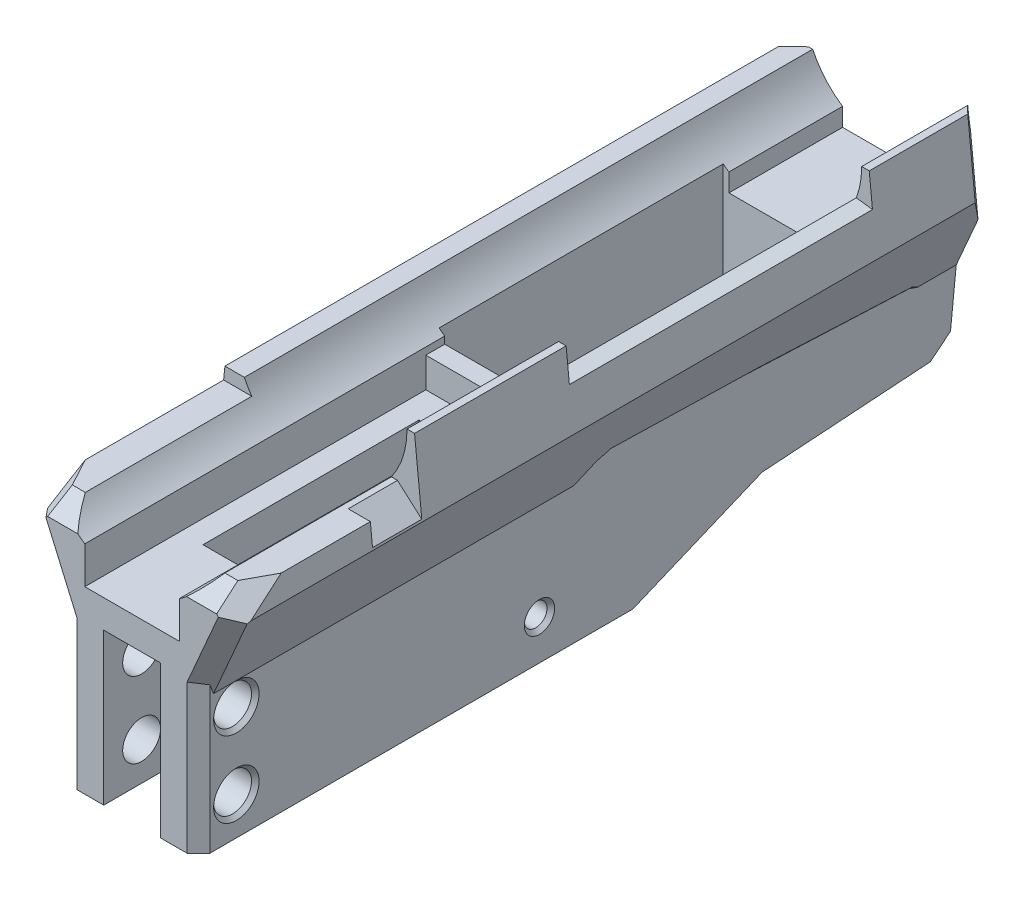
SolidWorks part; units mm, degrees
ref_plane "정면" through (0, 0, 0) normal (0, 0, 1) x (1, 0, 0)
ref_plane "윗면" through (0, 0, 0) normal (0, 1, 0) x (1, 0, 0)
ref_plane "우측면" through (0, 0, 0) normal (1, 0, 0) x (0, 0, -1)
sketch "스케치2" plane through (0, 0, 0) normal (0, 0, 1) x (1, 0, 0)
  line L0 (12.5, -18.7684) -> (-12.5, -18.7684)
  line L1 (-24.5373, 0) -> (-22.55, 0)
  line L2 (12.5, -18.7684) -> (12.5, -28.5684)
  line L3 (12.5, -28.5684) -> (-12.5, -28.5684)
  line L4 (-12.5, -28.5684) -> (-12.5, -18.7684)
  line L5 (-17.5, -40) -> (-17.5, -76)
  line L6 (22.55, 0) -> (24.5373, 0)
  line L7 (-24.5373, 0) -> (-26.5, -19.3006)
  line L8 (-26.5, -19.3006) -> (-17.5, -40)
  line L9 (20.3807, -9.6503) -> (20.3254, -9.6503)
  line L10 (0, 0) -> (0, -74.7461) construction
  line L11 (24.5373, 0) -> (26.5, -19.3006)
  line L12 (26.5, -19.3006) -> (17.5, -40)
  line L13 (-17.5, -76) -> (17.5, -76)
  line L14 (17.5, -76) -> (17.5, -40)
  line L15 (-20.3254, -9.6503) -> (-25.5187, -9.6503)
  arc A0 (-22.55, 0) -> (-12.5, -18.7684) centre (0, 0) ccw
  arc A1 (12.4817, -18.7205) -> (-12.4127, -18.7663) centre (0, 0) ccw construction
  arc A2 (12.5, -18.7684) -> (22.55, 0) centre (0, 0) ccw
  point P18 (0, -37.9251)
  dimension "D1" = 45.1
  dimension "D2" = 45
  dimension "D3" = 25
  dimension "D4" = 9.8
  dimension "D5" = 36
  dimension "D6" = 40
  dimension "D7" = 35
  dimension "D8" = 53
extrude "보스-돌출1" add sketch "스케치2" along normal blind 90 contours A2 A0 L1 L7 L8 L12 L11 L6 region at (0.3351, -45.0975, 0)
sketch "스케치3" plane through (0, -28.5684, 0) normal (0, 1, 0) x (1, 0, 0)
  line L0 (0, 0) -> (0, -90) construction
  line L1 (-6.5, -7.8) -> (6.5, -7.8)
  line L2 (-6.5, -7.8) -> (-6.5, -64.8)
  line L3 (-6.5, -64.8) -> (6.5, -64.8)
  line L4 (6.5, -7.8) -> (6.5, -64.8)
  line L5 (-6.5, -7.8) -> (6.5, -64.8) construction
  line L6 (-6.5, -64.8) -> (6.5, -7.8) construction
  line L7 (12.5, -90) -> (-12.5, -90) construction
  line L8 (12.5, 0) -> (-12.5, 0) construction
  point P0 (0, -36.3)
  dimension "D1" = 13
  dimension "D2" = 7.8
  dimension "D3" = 57
extrude "컷-돌출1" cut sketch "스케치3" against normal blind 45
sketch "스케치4" plane through (0, -73.5684, 0) normal (0, 1, 0) x (1, 0, 0)
  line L0 (-6.5, -7.8) -> (-6.5, -64.8) construction
  line L1 (-6.5, -24) -> (6.5, -24)
  line L2 (-6.5, -24) -> (-6.5, -50)
  line L3 (-6.5, -50) -> (6.5, -50)
  line L4 (6.5, -24) -> (6.5, -50)
  line L5 (6.5, -64.8) -> (6.5, -7.8) construction
  dimension "D1" = 26
  dimension "D2" = 24
extrude "컷-돌출2" cut sketch "스케치4" against normal up to next
chamfer "모따기1" distance 3 angle 45 2 edges at (0, -76, 24) (0, -76, 50)
sketch "스케치5" plane through (0, 0, 0) normal (1, 0, 0) x (0, 0, -1)
  line L0 (0, 0) -> (0, -19.3006) construction
  line L1 (-90, 0) -> (-40, 0)
  line L2 (-90, 0) -> (-90, -13)
  line L3 (-90, -13) -> (-40, -13)
  line L4 (-40, 0) -> (-40, -13)
  line L6 (-90, 0) -> (-90, -19.3006) construction
  dimension "D1" = 40
  dimension "D2" = 13
extrude "컷-돌출3" cut sketch "스케치5" against normal through all both and the other way through all
sketch "스케치7" plane through (0, 0, 40) normal (0, 0, 1) x (1, 0, 0)
  line L0 (20.0202, -13) -> (26.4361, -18.6724)
  line L2 (25.8593, -13) -> (26.5, -19.3006) construction
  line L3 (26.4361, -18.6724) -> (25.8593, -13)
  line L4 (25.8593, -13) -> (20.0202, -13)
  line L5 (18.4256, -13) -> (25.8593, -13) construction
extrude "컷-돌출5" cut sketch "스케치7" along normal blind 13
sketch "스케치9" plane through (0, 0, 0) normal (0, 0, -1) x (-1, 0, 0)
  line L0 (-25.3937, -8.4217) -> (-21.1393, -7.8507)
  line L1 (-24.5373, 0) -> (-26.5, -19.3006) construction
  line L3 (17.5, -76) -> (-17.5, -76) construction
  line L25 (-25.3937, -8.4217) -> (-26.5, -19.3006)
  line L26 (-26.5, -19.3006) -> (-17.5, -40)
  line L27 (-17.5, -40) -> (-17.5, -76)
  line L28 (-17.5, -76) -> (17.5, -76)
  line L29 (17.5, -76) -> (17.5, -40)
  line L30 (17.5, -40) -> (26.5, -19.3006)
  line L31 (26.5, -19.3006) -> (25.5187, -9.6503)
  line L32 (25.5187, -9.6503) -> (20.3807, -9.6503)
  line L33 (12.5, -18.7684) -> (12.5, -20.6394)
  line L34 (12.5, -20.6394) -> (-12.5, -20.6394)
  line L35 (-12.5, -20.6394) -> (-12.5, -18.7684)
  arc A0 (-22.55, 0) -> (-12.5, -18.7684) centre (0, 0) ccw construction
  arc A4 (-21.1393, -7.8507) -> (-12.5, -18.7684) centre (0, 0) ccw
  arc A5 (12.5, -18.7684) -> (20.3807, -9.6503) centre (0, 0) ccw
extrude "보스-돌출3" add sketch "스케치9" along normal blind 80
sketch "스케치12" plane through (0, 0, -80) normal (0, 0, -1) x (-1, 0, 0)
  line L0 (-12.5, -23.5684) -> (12.5, -23.5684)
  line L3 (-17.5, -76) -> (17.5, -76)
  line L9 (-12.5, -18.7684) -> (-12.5, -23.5684)
  line L11 (12.5, -23.5684) -> (12.5, -18.7684)
  line L24 (-25.3937, -8.4217) -> (-26.5, -19.3006)
  line L25 (-26.5, -19.3006) -> (-17.5, -40)
  line L26 (-17.5, -40) -> (-17.5, -76)
  line L28 (17.5, -76) -> (17.5, -40)
  line L29 (17.5, -40) -> (26.5, -19.3006)
  line L30 (26.5, -19.3006) -> (25.5187, -9.6503)
  line L31 (25.5187, -9.6503) -> (20.3807, -9.6503)
  line L40 (-22.55, 0) -> (-24.5373, 0)
  line L41 (-24.5373, 0) -> (-25.3937, -8.4217)
  arc A4 (12.5, -18.7684) -> (20.3807, -9.6503) centre (0, 0) ccw
  arc A5 (-21.1393, -7.8507) -> (-12.5, -18.7684) centre (0, 0) ccw
  arc A9 (-22.55, 0) -> (-21.1393, -7.8507) centre (0, 0) ccw
  dimension "D1" = 4.8
  dimension "D2" = 4.8
extrude "보스-돌출4" add sketch "스케치12" along normal blind 30
sketch "스케치13" plane through (0, -76, 0) normal (0, -1, 0) x (1, 0, 0)
  line L0 (0, 0) -> (0, -110) construction
  line L1 (-14, -5) -> (14, -5)
  line L2 (-14, -5) -> (-14, -80)
  line L3 (-14, -80) -> (14, -80)
  line L4 (14, -5) -> (14, -80)
  line L5 (-14, -5) -> (14, -80) construction
  line L6 (-14, -80) -> (14, -5) construction
  line L8 (17.5, -110) -> (-17.5, -110) construction
  point P0 (0, -42.5)
  dimension "D1" = 75
  dimension "D2" = 28
  dimension "D3" = 30
extrude "컷-돌출7" cut sketch "스케치13" against normal up to surface (69.1074 mm away) up to face at (22.2029, -7.9934, -60)
sketch "스케치14" plane through (0, 0, 0) normal (1, 0, 0) x (0, 0, -1)
  line L0 (5, -17.6777) -> (5, -76) construction
  line L1 (5, -46.8389) -> (-5, -46.8389)
  line L2 (5, -46.8389) -> (5, -76)
  line L3 (5, -76) -> (-5, -76)
  line L4 (-5, -46.8389) -> (-5, -76)
  line L5 (-90, -76) -> (110, -76) construction
  dimension "D1" = 10
extrude "컷-돌출8" cut sketch "스케치14" against normal mid plane 10
sketch "스케치15" plane through (17.5, 0, 0) normal (1, 0, 0) x (0, 0, -1)
  line L0 (-5, -46.8389) -> (-5, -76) construction
  circle A0 centre (0, -65.4709) radius 2
  dimension "D1" = 4
  dimension "D2" = 5
extrude "컷-돌출9" cut sketch "스케치15" against normal through all
sketch "스케치16" plane through (17.5, 0, 0) normal (1, 0, 0) x (0, 0, -1)
  circle A0 centre (0, -65.4709) radius 3
  dimension "D1" = 6
extrude "컷-돌출10" cut sketch "스케치16" against normal blind 14
sketch "스케치17" plane through (-17.5, 0, 0) normal (-1, 0, 0) x (0, 0, 1)
  circle A0 centre (0, -65.4709) radius 3
extrude "컷-돌출11" cut sketch "스케치17" against normal blind 14
sketch "스케치20" plane through (0, 0, 0) normal (1, 0, 0) x (0, 0, -1)
  line L0 (24.6381, -76) -> (58.7708, -61.7598)
  line L1 (-90, -76) -> (110, -76) construction
  line L2 (58.7708, -61.7598) -> (108.0651, -58.4096)
  line L3 (110, -40) -> (110, -76) construction
  line L4 (110, -58.8857) -> (110, -79)
  line L5 (110, -79) -> (24.6381, -76)
  line L6 (108.0651, -58.4096) -> (110, -40)
  line L7 (110, -40) -> (110, -58.8857)
  dimension "D1" = 6
extrude "컷-돌출12" cut sketch "스케치20" against normal through all both and the other way through all
chamfer "모따기2" distance 4.4 angle 54 2 edges at (22.1424, -13, 90) (-22.1424, -13, 90) first distance on face at (0, -29.8445, 90)
sketch "스케치22" plane through (17.5, 0, 0) normal (1, 0, 0) x (0, 0, -1)
  line L0 (5, -40) -> (16.1877, -33.6185)
  line L2 (110, -40) -> (-90, -40) construction
  line L3 (5, -17.6777) -> (5, -76) construction
  line L4 (16.1877, -33.6185) -> (97.9831, -37.258)
  line L6 (97.9831, -37.258) -> (105.8273, -40)
  line L7 (105.8273, -40) -> (5, -40)
extrude "컷-돌출13" cut sketch "스케치22" along normal blind 10
mirror "대칭 복사1" about plane through (0, 0, 0) normal (1, 0, 0) of "컷-돌출13"
chamfer "모따기3" distance 2 angle 45 6 edges at (-17.5, -36.8092, -10.5938) (-17.5, -35.4382, -57.0854) (-17.5, -38.629, -101.9052) (17.5, -38.629, -101.9052) (17.5, -35.4382, -57.0854) (17.5, -36.8092, -10.5938)
chamfer "모따기4" distance 4 angle 45 1 edges at (0, -58.4096, -108.0651) first distance on face at (0, -49.2048, -109.0325)
chamfer "모따기5" distance 4 angle 45 6 edges at (-26.0093, -14.4755, -110) (25.5187, -9.6503, -110) (26.083, -15.2, 86.972) (-26.083, -15.2, 86.972) (-22, -29.6503, 90) (22, -29.6503, 90) first distance on face at (-26.0089, -14.4717, 17.7063) first distance on face at (25.5368, -9.8283, 2.3034) first distance on face at (21.2706, -15.2341, 87.0189) first distance on face at (-21.2706, -15.2341, 87.0189) first distance on face at (0, -31.0658, 90)
sketch "스케치25" plane through (0, 0, 0) normal (1, 0, 0) x (0, 0, -1)
  line L0 (-90, -76) -> (-90, -29.9683) construction
  line L1 (-90, -36) -> (-70, -36)
  line L2 (-90, -36) -> (-90, -76)
  line L3 (-90, -76) -> (-70, -76)
  line L4 (-70, -36) -> (-70, -76)
  line L5 (-90, -76) -> (24.6381, -76) construction
  dimension "D1" = 20
  dimension "D2" = 40
extrude "컷-돌출14" cut sketch "스케치25" against normal mid plane 15
sketch "스케치26" plane through (0, 0, -110) normal (0, 0, -1) x (-1, 0, 0)
  line L0 (0, 0) -> (0, -79.2881) construction
  line L1 (17.5, -40) -> (-17.5, -40) construction
  line L3 (-7.5, -50) -> (7.5, -50)
  line L4 (-7.5, -50) -> (-7.5, -40)
  line L5 (-7.5, -40) -> (7.5, -40)
  line L6 (7.5, -50) -> (7.5, -40)
  line L7 (-7.5, -50) -> (7.5, -40) construction
  line L8 (-7.5, -40) -> (7.5, -50) construction
  circle A0 centre (-10, -32) radius 5
  circle A1 centre (10, -32) radius 5
  point P9 (0, -45)
  dimension "D1" = 10
  dimension "D2" = 8
  dimension "D3" = 10
  dimension "D4" = 10
  dimension "D5" = 15
extrude "컷-돌출15" cut sketch "스케치26" against normal blind 20
chamfer "모따기6" distance 1 angle 45 5 edges at (-7.5, -45, -109.4745) (7.5, -45, -109.4745) (0, -50, -108.949) (5, -32, -110) (-5, -32, -110) first distance on face at (-7.5, -45, -99.7372) first distance on face at (7.5, -45, -99.7372) first distance on face at (0, -50, -99.4745) first distance on face at (-5, -32, -110)
sketch "스케치28" plane through (17.5, 0, 0) normal (1, 0, 0) x (0, 0, -1)
  line L0 (-80, -36) -> (-80, -76) construction
  line L1 (-70, -36) -> (-90, -36) construction
  line L2 (-90, -76) -> (24.6381, -76) construction
  circle A0 centre (-80, -46) radius 5
  circle A1 centre (-80, -66) radius 5
  dimension "D1" = 10
  dimension "D2" = 10
  dimension "D3" = 10
  dimension "D4" = 10
extrude "컷-돌출16" cut sketch "스케치28" against normal through all
chamfer "모따기7" distance 1 angle 45 6 edges at (17.5, -62.4709, 0) (-17.5, -68.4709, 0) (-17.5, -61, 80) (-17.5, -41, 80) (17.5, -61, 80) (17.5, -41, 80)
chamfer "모따기8" distance 3 angle 45 2 edges at (-17.5, -52.9841, 90) (17.5, -52.9841, 90)
